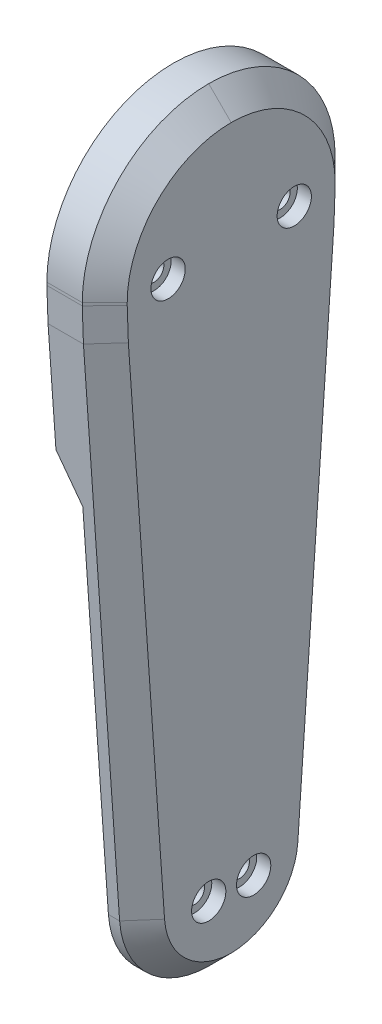
SolidWorks part; units mm, degrees
ref_plane "Front Plane" through (0, 0, 0) normal (0, 0, 1) x (1, 0, 0)
ref_plane "Top Plane" through (0, 0, 0) normal (0, 1, 0) x (1, 0, 0)
ref_plane "Right Plane" through (0, 0, 0) normal (1, 0, 0) x (0, 0, -1)
sketch "Sketch1" plane through (0, 0, 0) normal (1, 0, 0) x (0, 0, -1)
  line L1 (-10, 10) -> (10, 10)
  line L2 (-10, 10) -> (-10, -10)
  line L3 (-10, -10) -> (10, -10)
  line L4 (10, 10) -> (10, -10)
  line L5 (-10, 10) -> (10, -10) construction
  line L6 (-10, -10) -> (10, 10) construction
  point P0 (0, 0)
  dimension "D1" = 20
  dimension "D2" = 20
extrude "Boss-Extrude1" add sketch "Sketch1" along normal blind 20
sketch "Sketch2" plane through (20, 0, 0) normal (1, 0, 0) x (0, 0, -1)
  line L1 (-22.5, 35) -> (22.5, 35)
  line L2 (-22.5, 35) -> (-22.5, -35)
  line L3 (-22.5, -35) -> (22.5, -35)
  line L4 (22.5, 35) -> (22.5, -35)
  line L5 (-22.5, 35) -> (22.5, -35) construction
  line L6 (-22.5, -35) -> (22.5, 35) construction
  point P0 (0, 0)
  dimension "D1" = 45
  dimension "D2" = 70
extrude "Boss-Extrude2" add sketch "Sketch2" along normal blind 8.3
sketch "Sketch4" plane through (28.3, 0, 0) normal (1, 0, 0) x (0, 0, -1)
  line L0 (0, 7.65) -> (0, 8.1702) construction
  line L1 (7.65, 7.65) -> (-7.65, 7.65) construction
  line L17 (3.6, -26.55) -> (-3.6, -26.55) construction
  line L18 (-7.65, 7.65) -> (7.65, 7.65) construction
  line L22 (-7.65, 7.65) -> (-7.65, -27.55) construction
  line L23 (-7.65, -27.55) -> (7.65, -27.55) construction
  line L24 (7.65, 7.65) -> (7.65, -27.55) construction
  line L25 (-7.65, 7.65) -> (7.65, -27.55) construction
  line L26 (-7.65, -27.55) -> (7.65, 7.65) construction
  line L27 (3.6, -26.55) -> (3.6, -28.55) construction
  line L28 (3.6, -28.55) -> (-3.6, -28.55) construction
  line L29 (-3.6, -26.55) -> (-3.6, -28.55) construction
  line L30 (3.6, -26.55) -> (-3.6, -28.55) construction
  line L31 (3.6, -28.55) -> (-3.6, -26.55) construction
  line L34 (3.6, -28.55) -> (-3.6, -28.55)
  line L35 (-3.6, -28.55) -> (-3.6, -7.3118)
  line L36 (3.6, -28.55) -> (3.6, -7.3118)
  arc A1 (3.6, -6.75) -> (-3.6, -6.75) centre (0, 0) ccw construction
  arc A2 (3.6, -7.3118) -> (-3.6, -7.3118) centre (0, 0) ccw
  point P1 (0, -27.55)
  point P7 (0, -13.75)
  point P10 (0, 7.65)
  point P14 (0, -9.95)
  dimension "D1" = 15.3
  dimension "D5" = 2
  dimension "D2" = 15.3
  dimension "D3" = 35.2
  dimension "D4" = 7.2
extrude "Cut-Extrude1" cut sketch "Sketch4" against normal blind 5.8
fillet "Fillet1" radius 3.6 2 edges at (25.4, -28.55, 3.6) (25.4, -28.55, -3.6)
fillet "Fillet2" radius 10 2 edges at (25.4, -7.3118, 3.6) (25.4, -7.3118, -3.6)
sketch "Sketch5" plane through (0, 0, 0) normal (-1, 0, 0) x (0, 0, 1)
  circle A0 centre (0, 0) radius 3.9
  dimension "D1" = 7.8
extrude "Cut-Extrude2" cut sketch "Sketch5" against normal through all
sketch "Sketch6" plane through (22.5, 0, 0) normal (1, 0, 0) x (0, 0, -1)
  line L0 (0, -19.35) -> (0, 0) construction
  line L1 (0, -25.65) -> (0, -23.15) construction
  line L2 (0, -23.15) -> (0, -21.85) construction
  line L3 (0, -21.85) -> (0, -19.35) construction
  line L5 (0, 0) -> (1.164, 0) construction
  line L6 (0, 0) -> (0, -9.35) construction
  line L7 (0, -9.35) -> (1.164, -9.35) construction
  line L8 (1.164, 0) -> (1.164, -9.35) construction
  line L9 (0, 0) -> (1.164, -9.35) construction
  line L10 (0, -9.35) -> (1.164, 0) construction
  circle A0 centre (0, -20.6) radius 1.75
  circle A1 centre (0, -9.35) radius 1.75
  point P11 (0.582, -4.675)
  dimension "D5" = 3.5
  dimension "D6" = 9.35
  dimension "D7" = 3.5
  dimension "D1" = 19.35
  dimension "D2" = 2.5
  dimension "D3" = 1.3
  dimension "D4" = 2.5
extrude "Cut-Extrude3" cut sketch "Sketch6" against normal up to next
sketch "Sketch13" plane through (0, 0, 0) normal (-1, 0, 0) x (0, 0, 1)
  line L1 (-10, 10) -> (10, 10)
  line L2 (-10, 10) -> (-10, -10)
  line L3 (-10, -10) -> (10, -10)
  line L4 (10, 10) -> (10, -10)
extrude "Cut-Extrude9" cut sketch "Sketch13" against normal up to surface (20 mm away) up to face at (20, -20.6, -1.75)
sketch "Sketch15" plane through (0, 35, 0) normal (0, 1, 0) x (1, 0, 0)
  line L1 (20, 22.5) -> (28.3, 22.5)
  line L2 (20, 22.5) -> (20, -22.5)
  line L3 (20, -22.5) -> (28.3, -22.5)
  line L4 (28.3, 22.5) -> (28.3, -22.5)
extrude "Cut-Extrude10" cut sketch "Sketch15" against normal blind 12.5
sketch "Sketch18" plane through (0, -35, 0) normal (0, -1, 0) x (1, 0, 0)
  line L1 (20, 22.5) -> (28.3, 22.5)
  line L2 (20, 22.5) -> (20, -22.5)
  line L3 (20, -22.5) -> (28.3, -22.5)
  line L4 (28.3, 22.5) -> (28.3, -22.5)
  line L5 (28.3, 22.5) -> (20, 22.5) construction
  line L6 (28.3, 22.5) -> (28.3, -22.5) construction
extrude "Boss-Extrude4" add sketch "Sketch18" along normal blind 78.5
sketch "Sketch20" plane through (20, 0, 0) normal (-1, 0, 0) x (0, 0, 1)
  line L0 (0, 0) -> (0, -100) construction
  line L1 (22.5, 22.5) -> (22.5, -113.5) construction
  line L2 (-22.5, -113.5) -> (22.5, -113.5)
  line L3 (-22.5, -113.5) -> (-22.5, -33.5)
  line L4 (-22.5, -33.5) -> (22.5, -33.5)
  line L5 (22.5, -113.5) -> (22.5, -33.5)
  dimension "D1" = 100
  dimension "D2" = 80
fillet "Fillet5" radius 22.5 2 edges at (24.15, 22.5, -22.5) (24.15, 22.5, 22.5)
extrude "Cut-Extrude12" cut sketch "Sketch20" against normal blind 2.3
sketch "Sketch21" plane through (22.3, 0, 0) normal (-1, 0, 0) x (0, 0, 1)
  line L0 (0, -113.5) -> (0, -99.5) construction
  line L1 (-22.5, -113.5) -> (22.5, -113.5) construction
  line L2 (0, -99.5) -> (-8, -99.5) construction
  line L3 (0, -99.5) -> (8, -99.5) construction
  circle A0 centre (0, -99.5) radius 8 construction
  circle A1 centre (-4, -99.5) radius 1.75
  circle A2 centre (4, -99.5) radius 1.75
  dimension "D2" = 16
  dimension "D3" = 3.5
  dimension "D4" = 3.5
  dimension "D1" = 14
chamfer "Chamfer2" distance 110 angle 4 2 edges at (25.3, -113.5, -22.5) (25.3, -113.5, 22.5) first distance on face at (23.5333, -49, -22.5) first distance on face at (23.5333, -49, 22.5)
chamfer "Chamfer3" distance 3 angle 2 2 edges at (24.15, -3.5, 22.5) (24.15, -3.5, -22.5) first distance on face at (23.5333, -50.1667, 19.2367) first distance on face at (23.5333, -50.1667, -19.2367)
fillet "Fillet6" radius 16 2 edges at (25.3, -113.5, -14.8081) (25.3, -113.5, 14.8081)
chamfer "Chamfer4" distance 4 angle 45 10 edges at (28.3, -3.4963, -22.3954) (28.3, -0.25, -22.5) (28.3, 15.9099, -15.9099) (28.3, 15.9099, 15.9099) (28.3, -0.25, 22.5) (28.3, -3.4963, 22.3954) (28.3, -52.5544, 19.0698) (28.3, -109.1633, 10.8407) (28.3, -109.1633, -10.8407) (28.3, -52.5544, -19.0698)
sketch "Sketch14" plane through (20, 0, 0) normal (-1, 0, 0) x (0, 0, 1)
  line L0 (0, -11.1) -> (0, -18.85) construction
  line L1 (0, 0) -> (-5.975, 0) construction
  line L2 (0, 0) -> (5.975, 0) construction
  line L3 (-5.975, 0) -> (-16.475, 0) construction
  line L4 (5.975, 0) -> (16.475, 0) construction
  circle A0 centre (0, -9.35) radius 1.75 construction
  circle A1 centre (0, -20.6) radius 1.75 construction
  circle A3 centre (0, 0) radius 16.475 construction
  circle A4 centre (0, 0) radius 3.9 construction
  circle A5 centre (-11.225, 0) radius 1.75
  circle A6 centre (11.225, 0) radius 1.75
  point P7 (0, -14.975)
  dimension "D1" = 32.95
  dimension "D2" = 12.575
  dimension "D5" = 3.5
  dimension "D6" = 3.5
  dimension "D3" = 10.5
  dimension "D4" = 10.5
extrude "Cut-Extrude15" cut sketch "Sketch21" against normal through all
extrude "Cut-Extrude16" cut sketch "Sketch14" against normal through all contours A5 | A6
sketch "Sketch23" plane through (28.3, 0, 0) normal (1, 0, 0) x (0, 0, -1)
  line L1 (-8.5, 8.9) -> (8.5, 8.9)
  line L2 (-8.5, 8.9) -> (-8.5, -30)
  line L3 (-8.5, -30) -> (8.5, -30)
  line L4 (8.5, 8.9) -> (8.5, -30)
  dimension "D1" = 8.5
  dimension "D2" = 8.5
  dimension "D3" = 8.9
  dimension "D4" = 30
extrude "Boss-Extrude5" add sketch "Sketch23" against normal through all
sketch "Sketch24" plane through (20, 0, 0) normal (-1, 0, 0) x (0, 0, 1)
  line L7 (20.4022, -33.5) -> (22.2907, -6.4927)
  line L8 (22.2907, -6.4927) -> (22.5, -0.5)
  line L9 (22.5, -0.5) -> (22.5, 0)
  line L10 (-22.5, 0) -> (-22.5, -0.5)
  line L11 (-22.5, -0.5) -> (-22.2907, -6.4927)
  line L12 (-22.2907, -6.4927) -> (-20.4022, -33.5)
  line L13 (-20.4022, -33.5) -> (20.4022, -33.5)
  line L14 (20.4022, -33.5) -> (22.2907, -6.4927)
  line L15 (22.2907, -6.4927) -> (22.5, -0.5)
  line L16 (22.5, -0.5) -> (22.5, 0)
  line L17 (-22.5, 0) -> (-22.5, -0.5)
  line L18 (-22.5, -0.5) -> (-22.2907, -6.4927)
  line L19 (-22.2907, -6.4927) -> (-20.4022, -33.5)
  line L20 (-20.4022, -33.5) -> (20.4022, -33.5)
  circle A0 centre (11.225, 0) radius 1.75 construction
  circle A1 centre (-11.225, 0) radius 1.75 construction
  arc A2 (22.5, 0) -> (0, 22.5) centre (0, 0) ccw
  arc A3 (0, 22.5) -> (-22.5, 0) centre (0, 0) ccw
  arc A4 (22.5, 0) -> (0, 22.5) centre (0, 0) ccw
  arc A5 (0, 22.5) -> (-22.5, 0) centre (0, 0) ccw
  circle A6 centre (11.225, 0) radius 1.75
  circle A7 centre (-11.225, 0) radius 1.75
  dimension "D1" = 0
extrude "Boss-Extrude6" add sketch "Sketch24" along normal blind 2 contours L14 L15 L16 A4 A5 L17 L18 L19 L20 | A6 | A7
chamfer "Chamfer5" distance 4.3 angle 58 1 edges at (18, -33.5, 0) first distance on face at (20.15, -33.5, 0)
sketch "Sketch25" plane through (28.3, 0, 0) normal (1, 0, 0) x (0, 0, -1)
  circle A0 centre (-11.225, 0) radius 3.05
  circle A1 centre (11.225, 0) radius 3.05
  circle A2 centre (-4, -99.5) radius 3.05
  circle A3 centre (4, -99.5) radius 3.05
  dimension "D1" = 6.1
  dimension "D2" = 6.1
  dimension "D3" = 6.1
  dimension "D4" = 6.1
extrude "Cut-Extrude17" cut sketch "Sketch25" against normal blind 2.5
